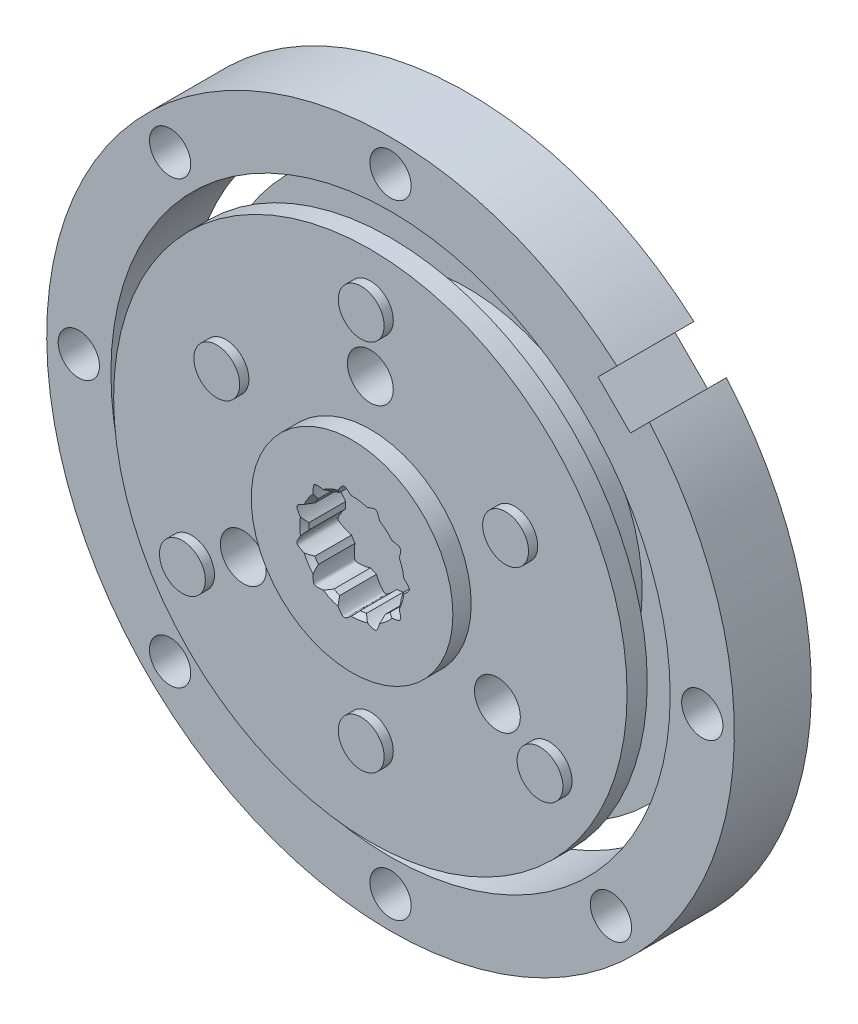
SolidWorks part; units mm, degrees
material "合金钢"
ref_plane "前视基准面" through (0, 0, 0) normal (0, 0, 1) x (1, 0, 0)
ref_plane "上视基准面" through (0, 0, 0) normal (0, 1, 0) x (1, 0, 0)
ref_plane "右视基准面" through (0, 0, 0) normal (1, 0, 0) x (0, 0, -1)
ref_axis "基准轴1" through (0, 0, 55) along (0, 0, -1)
sketch "旋转草图内花键" plane through (0, 0, 0) normal (1, 0, 0) x (0, 0, -1)
  line L0 (0, 0) -> (1, 0) construction
  line L1 (-12.7, 5.2) -> (-12.7, 19.05)
  line L2 (-12.7, 19.05) -> (12.7, 19.05)
  line L3 (12.7, 19.05) -> (12.7, 5.2)
  line L4 (12.7, 5.2) -> (-12.7, 5.2)
revolve "内花键" add sketch "旋转草图内花键" angle 360 about L0
sketch "齿草图内花键" plane through (0, 0, 0) normal (0, 0, 1) x (1, 0, 0)
  arc A0 (4.469, -1.3848) -> (4.469, 1.3848) centre (0, 0) ccw
  spline S0 degree 3 poles (4.469, 1.3848) (4.5766, 1.3527) (4.7413, 1.292) (4.9613, 1.1888) (5.1395, 1.0919) (5.3233, 0.9774) (5.5112, 0.8441) (5.7013, 0.6912) (5.8934, 0.5188) (6.0538, 0.3498) (6.1648, 0.2366) (6.2079, 0.1723) (6.2223, 0.1454) (6.2343, 0.1173) (6.2438, 0.0883) (6.257, 0.0305) (6.257, -0.0305) (6.2438, -0.0883) (6.2343, -0.1173) (6.2223, -0.1454) (6.2079, -0.1723) (6.1648, -0.2366) (6.0538, -0.3498) (5.8934, -0.5188) (5.7013, -0.6912) (5.5112, -0.8441) (5.3233, -0.9774) (5.1395, -1.0919) (4.9613, -1.1888) (4.7413, -1.292) (4.5766, -1.3527) (4.469, -1.3848) knots 0 0 0 0 0.072254 0.112805 0.156306 0.202756 0.252156 0.304505 0.359804 0.418052 0.454758 0.461299 0.467839 0.47438 0.48092 0.487461 0.512539 0.51908 0.52562 0.532161 0.538701 0.545242 0.581948 0.640196 0.695495 0.747844 0.797244 0.843694 0.887195 0.927746 1 1 1 1
extrude "齿拉伸切除内花键" cut sketch "齿草图内花键" against normal blind 12.7 and the other way blind 12.7
pattern_circular "齿形内花键" count 11 every 32.727 about axis through (0, 0, 55) along (0, 0, -1) of "齿拉伸切除内花键"
sketch "辅助草图内花键" plane through (0, 0, 0) normal (0, 0, 1) x (1, 0, 0)
  circle A0 centre (0, 0) radius 5.5 construction
  circle A1 centre (0, 0) radius 6.06 construction
  dimension "PitchDiameter" = 11
  dimension "FormDiameter" = 12.12
sketch "草图1" plane through (0, 0, 12.7) normal (0, 0, 1) x (1, 0, 0)
  circle A0 centre (0, 0) radius 11
  circle A1 centre (0, 0) radius 19.05 construction
  circle A2 centre (0, 0) radius 19.05
  dimension "D1" = 22
extrude "切除-拉伸1" cut sketch "草图1" against normal blind 2
sketch "草图2" plane through (0, 0, 10.7) normal (0, 0, 1) x (1, 0, 0)
  circle A0 centre (0, 0) radius 28
  circle A1 centre (0, 0) radius 19.05 construction
  circle A2 centre (0, 0) radius 19.05
  dimension "D1" = 56
extrude "凸台-拉伸1" add sketch "草图2" against normal blind 2.2
ref_plane "基准面1" through (0, 0, 8.5) normal (0, 0, 1) x (1, 0, 0)
sketch "草图4" plane through (0, 0, 8.5) normal (0, 0, 1) x (1, 0, 0)
  circle A0 centre (0, 0) radius 30.5
  circle A1 centre (0, 0) radius 37.5
  dimension "D1" = 61
  dimension "D2" = 75
extrude "凸台-拉伸3" add sketch "草图4" against normal blind 8.4 separate body
ref_plane "基准面2" through (0, 0, 4.3) normal (0, 0, 1) x (1, 0, 0)
mirror "镜向1" about plane through (0, 0, 4.3) normal (0, 0, 1) of "凸台-拉伸1"
sketch "草图5" plane through (0, 0, -12.7) normal (0, 0, -1) x (-1, 0, 0)
  circle A0 centre (0, 0) radius 19.05
extrude "切除-拉伸2" cut sketch "草图5" against normal up to surface (10.6 mm away) up to face at (28, 0, -2.1)
sketch "草图6" plane through (0, 0, -2.1) normal (0, 0, -1) x (-1, 0, 0)
  circle A1 centre (0, 0) radius 7.3279
extrude "凸台-拉伸4" add sketch "草图6" against normal blind 10.3
sketch "草图7" plane through (0, 0, -2.1) normal (0, 0, -1) x (-1, 0, 0)
  circle A0 centre (0, 0) radius 5
  dimension "D1" = 10
extrude "凸台-拉伸5" add sketch "草图7" along normal blind 2
sketch "草图8" plane through (0, 0, -4.1) normal (0, 0, -1) x (-1, 0, 0)
  arc A0 (4.2033, 4.2816) -> (3.6398, 4.7699) centre (0, 0) ccw
  arc A1 (1.2213, 5.8744) -> (0.4832, 5.9805) centre (0, 0) ccw
  arc A2 (-2.1485, 5.6021) -> (-2.8268, 5.2924) centre (0, 0) ccw
  arc A3 (-4.8362, 3.5512) -> (-5.2393, 2.9239) centre (0, 0) ccw
  arc A4 (-5.9884, 0.3728) -> (-5.9884, -0.3728) centre (0, 0) ccw
  arc A5 (-5.2393, -2.9239) -> (-4.8362, -3.5512) centre (0, 0) ccw
  arc A6 (-2.8268, -5.2924) -> (-2.1485, -5.6021) centre (0, 0) ccw
  arc A7 (0.4832, -5.9805) -> (1.2213, -5.8744) centre (0, 0) ccw
  arc A8 (3.6398, -4.7699) -> (4.2033, -4.2816) centre (0, 0) ccw
  arc A9 (5.6408, -2.0449) -> (5.8509, -1.3294) centre (0, 0) ccw
  arc A10 (5.8509, 1.3294) -> (5.6408, 2.0449) centre (0, 0) ccw
  spline S0 degree 3 poles (5.6408, 2.0449) (5.6059, 2.0647) (5.5481, 2.0966) (5.4671, 2.1391) (5.3987, 2.1734) (5.3308, 2.206) (5.2634, 2.2369) (5.1966, 2.2661) (5.1304, 2.2937) (5.0648, 2.3197) (4.9999, 2.3441) (4.9357, 2.367) (4.8723, 2.3883) (4.8096, 2.4082) (4.7477, 2.4266) (4.6867, 2.4436) (4.6265, 2.4593) (4.5673, 2.4736) (4.4879, 2.4914) (4.4166, 2.5045) (4.3542, 2.5189) (4.3219, 2.5307) (4.2909, 2.5455) (4.2615, 2.5634) (4.2341, 2.5842) (4.2089, 2.6077) (4.1862, 2.6335) (4.1704, 2.6559) (4.1595, 2.6732) (4.1484, 2.6902) (4.1345, 2.7139) (4.1205, 2.7453) (4.1096, 2.7779) (4.1021, 2.8115) (4.098, 2.8457) (4.0974, 2.88) (4.1001, 2.9144) (4.1129, 2.9771) (4.1306, 3.0474) (4.1474, 3.127) (4.159, 3.1868) (4.1697, 3.248) (4.1796, 3.3106) (4.1885, 3.3746) (4.1965, 3.4398) (4.2034, 3.5064) (4.2093, 3.5743) (4.214, 3.6435) (4.2177, 3.7139) (4.2201, 3.7856) (4.2212, 3.8585) (4.2211, 3.9326) (4.2197, 4.0079) (4.2169, 4.0844) (4.2119, 4.1758) (4.2069, 4.2416) (4.2033, 4.2816) knots 0.01157 0.01157 0.01157 0.01157 0.047599 0.070861 0.093765 0.116312 0.1385 0.16033 0.181802 0.202916 0.223673 0.244071 0.264111 0.283793 0.303117 0.322083 0.340691 0.358941 0.376833 0.413736 0.424017 0.434298 0.444579 0.45486 0.465141 0.475422 0.485703 0.495984 0.5 0.504016 0.514297 0.524578 0.534859 0.54514 0.555421 0.565702 0.575983 0.586264 0.623167 0.641059 0.659309 0.677917 0.696883 0.716207 0.735889 0.755929 0.776327 0.797084 0.818198 0.83967 0.8615 0.883688 0.906235 0.929139 0.952401 0.98843 0.98843 0.98843 0.98843
  spline S1 degree 3 poles (3.6398, 4.7699) (3.5997, 4.7677) (3.5339, 4.7634) (3.4427, 4.7552) (3.3666, 4.7471) (3.2919, 4.7378) (3.2185, 4.7274) (3.1465, 4.7159) (3.0759, 4.7033) (3.0067, 4.6897) (2.9389, 4.6751) (2.8725, 4.6597) (2.8076, 4.6433) (2.7441, 4.6262) (2.6821, 4.6082) (2.6216, 4.5895) (2.5625, 4.5702) (2.5049, 4.5502) (2.4285, 4.5223) (2.3615, 4.4947) (2.3012, 4.4731) (2.2676, 4.4656) (2.2335, 4.4612) (2.1991, 4.4604) (2.1648, 4.4631) (2.1309, 4.4692) (2.0979, 4.4787) (2.0725, 4.489) (2.054, 4.4976) (2.0354, 4.5059) (2.0109, 4.5184) (1.9821, 4.5372) (1.9553, 4.5587) (1.9309, 4.5829) (1.909, 4.6094) (1.8899, 4.6381) (1.8736, 4.6684) (1.8504, 4.7281) (1.8274, 4.7968) (1.7984, 4.8728) (1.7758, 4.9294) (1.7518, 4.9868) (1.7263, 5.0447) (1.6992, 5.1034) (1.6706, 5.1626) (1.6404, 5.2223) (1.6087, 5.2826) (1.5753, 5.3434) (1.5402, 5.4046) (1.5035, 5.4662) (1.4651, 5.5282) (1.4249, 5.5905) (1.383, 5.653) (1.3393, 5.7158) (1.2857, 5.7901) (1.2459, 5.8427) (1.2213, 5.8744) knots 0.01157 0.01157 0.01157 0.01157 0.047599 0.070861 0.093765 0.116312 0.1385 0.16033 0.181802 0.202916 0.223673 0.244071 0.264111 0.283793 0.303117 0.322083 0.340691 0.358941 0.376833 0.413736 0.424017 0.434298 0.444579 0.45486 0.465141 0.475422 0.485703 0.495984 0.5 0.504016 0.514297 0.524578 0.534859 0.54514 0.555421 0.565702 0.575983 0.586264 0.623167 0.641059 0.659309 0.677917 0.696883 0.716207 0.735889 0.755929 0.776327 0.797084 0.818198 0.83967 0.8615 0.883688 0.906235 0.929139 0.952401 0.98843 0.98843 0.98843 0.98843
  spline S2 degree 3 poles (0.4832, 5.9805) (0.4507, 5.9571) (0.3976, 5.9177) (0.3253, 5.8616) (0.2657, 5.8137) (0.2078, 5.7654) (0.1518, 5.717) (0.0974, 5.6684) (0.0448, 5.6196) (-0.0061, 5.5707) (-0.0552, 5.5218) (-0.1027, 5.4729) (-0.1485, 5.4241) (-0.1926, 5.3753) (-0.2351, 5.3267) (-0.2759, 5.2783) (-0.3151, 5.2301) (-0.3527, 5.1821) (-0.402, 5.1173) (-0.4434, 5.0579) (-0.4825, 5.0071) (-0.5066, 4.9826) (-0.533, 4.9605) (-0.5615, 4.9413) (-0.5918, 4.925) (-0.6236, 4.9118) (-0.6565, 4.9019) (-0.6835, 4.8968) (-0.7037, 4.8941) (-0.7238, 4.891) (-0.7511, 4.8883) (-0.7855, 4.8885) (-0.8197, 4.8922) (-0.8534, 4.8993) (-0.8861, 4.9098) (-0.9177, 4.9235) (-0.9478, 4.9402) (-0.9995, 4.9779) (-1.056, 5.0233) (-1.1215, 5.0716) (-1.1711, 5.107) (-1.2223, 5.1422) (-1.2752, 5.1772) (-1.3296, 5.2119) (-1.3857, 5.2462) (-1.4434, 5.2802) (-1.5027, 5.3137) (-1.5636, 5.3468) (-1.6262, 5.3793) (-1.6904, 5.4113) (-1.7563, 5.4427) (-1.8237, 5.4733) (-1.8928, 5.5033) (-1.9635, 5.5325) (-2.0487, 5.566) (-2.1107, 5.5888) (-2.1485, 5.6021) knots 0.01157 0.01157 0.01157 0.01157 0.047599 0.070861 0.093765 0.116312 0.1385 0.16033 0.181802 0.202916 0.223673 0.244071 0.264111 0.283793 0.303117 0.322083 0.340691 0.358941 0.376833 0.413736 0.424017 0.434298 0.444579 0.45486 0.465141 0.475422 0.485703 0.495984 0.5 0.504016 0.514297 0.524578 0.534859 0.54514 0.555421 0.565702 0.575983 0.586264 0.623167 0.641059 0.659309 0.677917 0.696883 0.716207 0.735889 0.755929 0.776327 0.797084 0.818198 0.83967 0.8615 0.883688 0.906235 0.929139 0.952401 0.98843 0.98843 0.98843 0.98843
  spline S3 degree 3 poles (-2.8268, 5.2924) (-2.8415, 5.255) (-2.8649, 5.1933) (-2.8954, 5.107) (-2.9196, 5.0344) (-2.9422, 4.9626) (-2.9632, 4.8915) (-2.9826, 4.8212) (-3.0005, 4.7517) (-3.0169, 4.6831) (-3.0318, 4.6154) (-3.0453, 4.5486) (-3.0574, 4.4828) (-3.0682, 4.4179) (-3.0776, 4.3541) (-3.0858, 4.2912) (-3.0927, 4.2294) (-3.0984, 4.1688) (-3.1048, 4.0877) (-3.1075, 4.0153) (-3.1129, 3.9514) (-3.12, 3.9177) (-3.1303, 3.8849) (-3.1438, 3.8533) (-3.1605, 3.8232) (-3.1801, 3.795) (-3.2024, 3.7688) (-3.2224, 3.75) (-3.2379, 3.7368) (-3.2532, 3.7233) (-3.2747, 3.7062) (-3.3037, 3.6878) (-3.3345, 3.6724) (-3.3667, 3.6602) (-3.3999, 3.6513) (-3.4338, 3.6458) (-3.4682, 3.6436) (-3.5321, 3.6473) (-3.6042, 3.6549) (-3.6854, 3.6601) (-3.7463, 3.6631) (-3.8084, 3.6651) (-3.8717, 3.6659) (-3.9363, 3.6657) (-4.002, 3.6642) (-4.0689, 3.6616) (-4.137, 3.6578) (-4.2061, 3.6526) (-4.2763, 3.6462) (-4.3476, 3.6384) (-4.42, 3.6291) (-4.4933, 3.6185) (-4.5677, 3.6064) (-4.643, 3.5927) (-4.7327, 3.5748) (-4.7972, 3.5605) (-4.8362, 3.5512) knots 0.01157 0.01157 0.01157 0.01157 0.047599 0.070861 0.093765 0.116312 0.1385 0.16033 0.181802 0.202916 0.223673 0.244071 0.264111 0.283793 0.303117 0.322083 0.340691 0.358941 0.376833 0.413736 0.424017 0.434298 0.444579 0.45486 0.465141 0.475422 0.485703 0.495984 0.5 0.504016 0.514297 0.524578 0.534859 0.54514 0.555421 0.565702 0.575983 0.586264 0.623167 0.641059 0.659309 0.677917 0.696883 0.716207 0.735889 0.755929 0.776327 0.797084 0.818198 0.83967 0.8615 0.883688 0.906235 0.929139 0.952401 0.98843 0.98843 0.98843 0.98843
  spline S4 degree 3 poles (-5.2393, 2.9239) (-5.2315, 2.8846) (-5.2178, 2.82) (-5.1968, 2.7309) (-5.1779, 2.6568) (-5.1581, 2.5841) (-5.1373, 2.513) (-5.1156, 2.4433) (-5.0931, 2.3752) (-5.0698, 2.3086) (-5.0458, 2.2436) (-5.021, 2.1801) (-4.9956, 2.1182) (-4.9696, 2.0578) (-4.943, 1.999) (-4.9159, 1.9417) (-4.8884, 1.886) (-4.8603, 1.8319) (-4.8219, 1.7602) (-4.785, 1.6978) (-4.7551, 1.6412) (-4.7428, 1.609) (-4.7337, 1.5759) (-4.728, 1.5419) (-4.7257, 1.5076) (-4.727, 1.4732) (-4.7316, 1.4391) (-4.7382, 1.4125) (-4.7442, 1.393) (-4.7497, 1.3734) (-4.7585, 1.3474) (-4.7731, 1.3163) (-4.7906, 1.2867) (-4.8111, 1.259) (-4.8342, 1.2335) (-4.8598, 1.2106) (-4.8875, 1.1901) (-4.9433, 1.1587) (-5.008, 1.1261) (-5.0792, 1.0866) (-5.132, 1.0562) (-5.1853, 1.0243) (-5.2391, 0.9907) (-5.2932, 0.9556) (-5.3478, 0.9189) (-5.4026, 0.8805) (-5.4578, 0.8405) (-5.5132, 0.7988) (-5.5688, 0.7554) (-5.6245, 0.7103) (-5.6804, 0.6634) (-5.7363, 0.6148) (-5.7923, 0.5644) (-5.8483, 0.5122) (-5.9141, 0.4486) (-5.9606, 0.4017) (-5.9884, 0.3728) knots 0.01157 0.01157 0.01157 0.01157 0.047599 0.070861 0.093765 0.116312 0.1385 0.16033 0.181802 0.202916 0.223673 0.244071 0.264111 0.283793 0.303117 0.322083 0.340691 0.358941 0.376833 0.413736 0.424017 0.434298 0.444579 0.45486 0.465141 0.475422 0.485703 0.495984 0.5 0.504016 0.514297 0.524578 0.534859 0.54514 0.555421 0.565702 0.575983 0.586264 0.623167 0.641059 0.659309 0.677917 0.696883 0.716207 0.735889 0.755929 0.776327 0.797084 0.818198 0.83967 0.8615 0.883688 0.906235 0.929139 0.952401 0.98843 0.98843 0.98843 0.98843
  spline S5 degree 3 poles (-5.9884, -0.3728) (-5.9606, -0.4017) (-5.9141, -0.4486) (-5.8483, -0.5122) (-5.7923, -0.5644) (-5.7363, -0.6148) (-5.6804, -0.6634) (-5.6245, -0.7103) (-5.5688, -0.7554) (-5.5132, -0.7988) (-5.4578, -0.8405) (-5.4026, -0.8805) (-5.3478, -0.9189) (-5.2932, -0.9556) (-5.2391, -0.9907) (-5.1853, -1.0243) (-5.132, -1.0562) (-5.0792, -1.0866) (-5.008, -1.1261) (-4.9433, -1.1587) (-4.8875, -1.1901) (-4.8598, -1.2106) (-4.8342, -1.2335) (-4.8111, -1.259) (-4.7906, -1.2867) (-4.7731, -1.3163) (-4.7585, -1.3474) (-4.7497, -1.3734) (-4.7442, -1.393) (-4.7382, -1.4125) (-4.7316, -1.4391) (-4.727, -1.4732) (-4.7257, -1.5076) (-4.728, -1.5419) (-4.7337, -1.5759) (-4.7428, -1.609) (-4.7551, -1.6412) (-4.785, -1.6978) (-4.8219, -1.7602) (-4.8603, -1.8319) (-4.8884, -1.886) (-4.9159, -1.9417) (-4.943, -1.999) (-4.9696, -2.0578) (-4.9956, -2.1182) (-5.021, -2.1801) (-5.0458, -2.2436) (-5.0698, -2.3086) (-5.0931, -2.3752) (-5.1156, -2.4433) (-5.1373, -2.513) (-5.1581, -2.5841) (-5.1779, -2.6568) (-5.1968, -2.7309) (-5.2178, -2.82) (-5.2315, -2.8846) (-5.2393, -2.9239) knots 0.01157 0.01157 0.01157 0.01157 0.047599 0.070861 0.093765 0.116312 0.1385 0.16033 0.181802 0.202916 0.223673 0.244071 0.264111 0.283793 0.303117 0.322083 0.340691 0.358941 0.376833 0.413736 0.424017 0.434298 0.444579 0.45486 0.465141 0.475422 0.485703 0.495984 0.5 0.504016 0.514297 0.524578 0.534859 0.54514 0.555421 0.565702 0.575983 0.586264 0.623167 0.641059 0.659309 0.677917 0.696883 0.716207 0.735889 0.755929 0.776327 0.797084 0.818198 0.83967 0.8615 0.883688 0.906235 0.929139 0.952401 0.98843 0.98843 0.98843 0.98843
  spline S6 degree 3 poles (-4.8362, -3.5512) (-4.7972, -3.5605) (-4.7327, -3.5748) (-4.643, -3.5927) (-4.5677, -3.6064) (-4.4933, -3.6185) (-4.42, -3.6291) (-4.3476, -3.6384) (-4.2763, -3.6462) (-4.2061, -3.6526) (-4.137, -3.6578) (-4.0689, -3.6616) (-4.002, -3.6642) (-3.9363, -3.6657) (-3.8717, -3.6659) (-3.8084, -3.6651) (-3.7463, -3.6631) (-3.6854, -3.6601) (-3.6042, -3.6549) (-3.5321, -3.6473) (-3.4682, -3.6436) (-3.4338, -3.6458) (-3.3999, -3.6513) (-3.3667, -3.6602) (-3.3345, -3.6724) (-3.3037, -3.6878) (-3.2747, -3.7062) (-3.2532, -3.7233) (-3.2379, -3.7368) (-3.2224, -3.75) (-3.2024, -3.7688) (-3.1801, -3.795) (-3.1605, -3.8232) (-3.1438, -3.8533) (-3.1303, -3.8849) (-3.12, -3.9177) (-3.1129, -3.9514) (-3.1075, -4.0153) (-3.1048, -4.0877) (-3.0984, -4.1688) (-3.0927, -4.2294) (-3.0858, -4.2912) (-3.0776, -4.3541) (-3.0682, -4.4179) (-3.0574, -4.4828) (-3.0453, -4.5486) (-3.0318, -4.6154) (-3.0169, -4.6831) (-3.0005, -4.7517) (-2.9826, -4.8212) (-2.9632, -4.8915) (-2.9422, -4.9626) (-2.9196, -5.0344) (-2.8954, -5.107) (-2.8649, -5.1933) (-2.8415, -5.255) (-2.8268, -5.2924) knots 0.01157 0.01157 0.01157 0.01157 0.047599 0.070861 0.093765 0.116312 0.1385 0.16033 0.181802 0.202916 0.223673 0.244071 0.264111 0.283793 0.303117 0.322083 0.340691 0.358941 0.376833 0.413736 0.424017 0.434298 0.444579 0.45486 0.465141 0.475422 0.485703 0.495984 0.5 0.504016 0.514297 0.524578 0.534859 0.54514 0.555421 0.565702 0.575983 0.586264 0.623167 0.641059 0.659309 0.677917 0.696883 0.716207 0.735889 0.755929 0.776327 0.797084 0.818198 0.83967 0.8615 0.883688 0.906235 0.929139 0.952401 0.98843 0.98843 0.98843 0.98843
  spline S7 degree 3 poles (-2.1485, -5.6021) (-2.1107, -5.5888) (-2.0487, -5.566) (-1.9635, -5.5325) (-1.8928, -5.5033) (-1.8237, -5.4733) (-1.7563, -5.4427) (-1.6904, -5.4113) (-1.6262, -5.3793) (-1.5636, -5.3468) (-1.5027, -5.3137) (-1.4434, -5.2802) (-1.3857, -5.2462) (-1.3296, -5.2119) (-1.2752, -5.1772) (-1.2223, -5.1422) (-1.1711, -5.107) (-1.1215, -5.0716) (-1.056, -5.0233) (-0.9995, -4.9779) (-0.9478, -4.9402) (-0.9177, -4.9235) (-0.8861, -4.9098) (-0.8534, -4.8993) (-0.8197, -4.8922) (-0.7855, -4.8885) (-0.7511, -4.8883) (-0.7238, -4.891) (-0.7037, -4.8941) (-0.6835, -4.8968) (-0.6565, -4.9019) (-0.6236, -4.9118) (-0.5918, -4.925) (-0.5615, -4.9413) (-0.533, -4.9605) (-0.5066, -4.9826) (-0.4825, -5.0071) (-0.4434, -5.0579) (-0.402, -5.1173) (-0.3527, -5.1821) (-0.3151, -5.2301) (-0.2759, -5.2783) (-0.2351, -5.3267) (-0.1926, -5.3753) (-0.1485, -5.4241) (-0.1027, -5.4729) (-0.0552, -5.5218) (-0.0061, -5.5707) (0.0448, -5.6196) (0.0974, -5.6684) (0.1518, -5.717) (0.2078, -5.7654) (0.2657, -5.8137) (0.3253, -5.8616) (0.3976, -5.9177) (0.4507, -5.9571) (0.4832, -5.9805) knots 0.01157 0.01157 0.01157 0.01157 0.047599 0.070861 0.093765 0.116312 0.1385 0.16033 0.181802 0.202916 0.223673 0.244071 0.264111 0.283793 0.303117 0.322083 0.340691 0.358941 0.376833 0.413736 0.424017 0.434298 0.444579 0.45486 0.465141 0.475422 0.485703 0.495984 0.5 0.504016 0.514297 0.524578 0.534859 0.54514 0.555421 0.565702 0.575983 0.586264 0.623167 0.641059 0.659309 0.677917 0.696883 0.716207 0.735889 0.755929 0.776327 0.797084 0.818198 0.83967 0.8615 0.883688 0.906235 0.929139 0.952401 0.98843 0.98843 0.98843 0.98843
  spline S8 degree 3 poles (1.2213, -5.8744) (1.2459, -5.8427) (1.2857, -5.7901) (1.3393, -5.7158) (1.383, -5.653) (1.4249, -5.5905) (1.4651, -5.5282) (1.5035, -5.4662) (1.5402, -5.4046) (1.5753, -5.3434) (1.6087, -5.2826) (1.6404, -5.2223) (1.6706, -5.1626) (1.6992, -5.1034) (1.7263, -5.0447) (1.7518, -4.9868) (1.7758, -4.9294) (1.7984, -4.8728) (1.8274, -4.7968) (1.8504, -4.7281) (1.8736, -4.6684) (1.8899, -4.6381) (1.909, -4.6094) (1.9309, -4.5829) (1.9553, -4.5587) (1.9821, -4.5372) (2.0109, -4.5184) (2.0354, -4.5059) (2.054, -4.4976) (2.0725, -4.489) (2.0979, -4.4787) (2.1309, -4.4692) (2.1648, -4.4631) (2.1991, -4.4604) (2.2335, -4.4612) (2.2676, -4.4656) (2.3012, -4.4731) (2.3615, -4.4947) (2.4285, -4.5223) (2.5049, -4.5502) (2.5625, -4.5702) (2.6216, -4.5895) (2.6821, -4.6082) (2.7441, -4.6262) (2.8076, -4.6433) (2.8725, -4.6597) (2.9389, -4.6751) (3.0067, -4.6897) (3.0759, -4.7033) (3.1465, -4.7159) (3.2185, -4.7274) (3.2919, -4.7378) (3.3666, -4.7471) (3.4427, -4.7552) (3.5339, -4.7634) (3.5997, -4.7677) (3.6398, -4.7699) knots 0.01157 0.01157 0.01157 0.01157 0.047599 0.070861 0.093765 0.116312 0.1385 0.16033 0.181802 0.202916 0.223673 0.244071 0.264111 0.283793 0.303117 0.322083 0.340691 0.358941 0.376833 0.413736 0.424017 0.434298 0.444579 0.45486 0.465141 0.475422 0.485703 0.495984 0.5 0.504016 0.514297 0.524578 0.534859 0.54514 0.555421 0.565702 0.575983 0.586264 0.623167 0.641059 0.659309 0.677917 0.696883 0.716207 0.735889 0.755929 0.776327 0.797084 0.818198 0.83967 0.8615 0.883688 0.906235 0.929139 0.952401 0.98843 0.98843 0.98843 0.98843
  spline S9 degree 3 poles (4.2033, -4.2816) (4.2069, -4.2416) (4.2119, -4.1758) (4.2169, -4.0844) (4.2197, -4.0079) (4.2211, -3.9326) (4.2212, -3.8585) (4.2201, -3.7856) (4.2177, -3.7139) (4.214, -3.6435) (4.2093, -3.5743) (4.2034, -3.5064) (4.1965, -3.4398) (4.1885, -3.3746) (4.1796, -3.3106) (4.1697, -3.248) (4.159, -3.1868) (4.1474, -3.127) (4.1306, -3.0474) (4.1129, -2.9771) (4.1001, -2.9144) (4.0974, -2.88) (4.098, -2.8457) (4.1021, -2.8115) (4.1096, -2.7779) (4.1205, -2.7453) (4.1345, -2.7139) (4.1484, -2.6902) (4.1595, -2.6732) (4.1704, -2.6559) (4.1862, -2.6335) (4.2089, -2.6077) (4.2341, -2.5842) (4.2615, -2.5634) (4.2909, -2.5455) (4.3219, -2.5307) (4.3542, -2.5189) (4.4166, -2.5045) (4.4879, -2.4914) (4.5673, -2.4736) (4.6265, -2.4593) (4.6867, -2.4436) (4.7477, -2.4266) (4.8096, -2.4082) (4.8723, -2.3883) (4.9357, -2.367) (4.9999, -2.3441) (5.0648, -2.3197) (5.1304, -2.2937) (5.1966, -2.2661) (5.2634, -2.2369) (5.3308, -2.206) (5.3987, -2.1734) (5.4671, -2.1391) (5.5481, -2.0966) (5.6059, -2.0647) (5.6408, -2.0449) knots 0.01157 0.01157 0.01157 0.01157 0.047599 0.070861 0.093765 0.116312 0.1385 0.16033 0.181802 0.202916 0.223673 0.244071 0.264111 0.283793 0.303117 0.322083 0.340691 0.358941 0.376833 0.413736 0.424017 0.434298 0.444579 0.45486 0.465141 0.475422 0.485703 0.495984 0.5 0.504016 0.514297 0.524578 0.534859 0.54514 0.555421 0.565702 0.575983 0.586264 0.623167 0.641059 0.659309 0.677917 0.696883 0.716207 0.735889 0.755929 0.776327 0.797084 0.818198 0.83967 0.8615 0.883688 0.906235 0.929139 0.952401 0.98843 0.98843 0.98843 0.98843
  spline S10 degree 3 poles (5.8509, -1.3294) (5.8323, -1.2939) (5.8009, -1.2358) (5.7557, -1.1562) (5.7167, -1.0904) (5.6772, -1.0262) (5.6372, -0.9638) (5.5968, -0.9031) (5.556, -0.8441) (5.5149, -0.7868) (5.4735, -0.7312) (5.4319, -0.6772) (5.39, -0.625) (5.348, -0.5744) (5.306, -0.5254) (5.2638, -0.4781) (5.2217, -0.4324) (5.1796, -0.3883) (5.1224, -0.3304) (5.0695, -0.2809) (5.0248, -0.235) (5.004, -0.2076) (4.9859, -0.1784) (4.9709, -0.1474) (4.9591, -0.1151) (4.9506, -0.0818) (4.9454, -0.0478) (4.9443, -0.0204) (4.9444, 0) (4.9443, 0.0204) (4.9454, 0.0478) (4.9506, 0.0818) (4.9591, 0.1151) (4.9709, 0.1474) (4.9859, 0.1784) (5.004, 0.2076) (5.0248, 0.235) (5.0695, 0.2809) (5.1224, 0.3304) (5.1796, 0.3883) (5.2217, 0.4324) (5.2638, 0.4781) (5.306, 0.5254) (5.348, 0.5744) (5.39, 0.625) (5.4319, 0.6772) (5.4735, 0.7312) (5.5149, 0.7868) (5.556, 0.8441) (5.5968, 0.9031) (5.6372, 0.9638) (5.6772, 1.0262) (5.7167, 1.0904) (5.7557, 1.1562) (5.8009, 1.2358) (5.8323, 1.2939) (5.8509, 1.3294) knots 0.01157 0.01157 0.01157 0.01157 0.047599 0.070861 0.093765 0.116312 0.1385 0.16033 0.181802 0.202916 0.223673 0.244071 0.264111 0.283793 0.303117 0.322083 0.340691 0.358941 0.376833 0.413736 0.424017 0.434298 0.444579 0.45486 0.465141 0.475422 0.485703 0.495984 0.5 0.504016 0.514297 0.524578 0.534859 0.54514 0.555421 0.565702 0.575983 0.586264 0.623167 0.641059 0.659309 0.677917 0.696883 0.716207 0.735889 0.755929 0.776327 0.797084 0.818198 0.83967 0.8615 0.883688 0.906235 0.929139 0.952401 0.98843 0.98843 0.98843 0.98843
extrude "凸台-拉伸6" add sketch "草图8" along normal blind 5.8
sketch "草图9" plane through (0, 0, 8.5) normal (0, 0, 1) x (1, 0, 0)
  line L0 (0, 0) -> (33.1112, 33.1112) construction
  line L1 (26.163, 22.6274) -> (28.2253, 24.6897)
  line L2 (22.6274, 26.163) -> (24.6897, 28.2253)
  line L3 (22.6274, 26.163) -> (26.163, 22.6274)
  line L5 (-1.7678, 1.7678) -> (31.3435, 34.879) construction
  line L6 (1.7678, -1.7678) -> (34.879, 31.3435) construction
  circle A0 centre (0, 0) radius 34 construction
  circle A1 centre (0, 34) radius 2.25
  circle A2 centre (24.0416, 24.0416) radius 2.25 construction
  circle A3 centre (34, 0) radius 2.25
  circle A4 centre (24.0416, -24.0416) radius 2.25
  circle A5 centre (0, -34) radius 2.25
  circle A6 centre (-24.0416, -24.0416) radius 2.25
  circle A7 centre (-34, 0) radius 2.25
  circle A8 centre (-24.0416, 24.0416) radius 2.25
  circle A9 centre (0, 0) radius 37.5 construction
  arc A10 (28.2253, 24.6897) -> (24.6897, 28.2253) centre (0, 0) ccw
  point P21 (0, 0)
  dimension "D1" = 68
  dimension "D2" = 4.5
  dimension "D6" = 34.5
  dimension "D4" = 2.5
  dimension "D5" = 2.5
  dimension "D3" = 8
extrude "切除-拉伸3" cut sketch "草图9" against normal up to surface (8.4 mm away) up to face at (30.5, 0, 0.1)
sketch "草图10" plane through (0, 0, 10.7) normal (0, 0, 1) x (1, 0, 0)
  line L0 (0, 0) -> (0, 34) construction
  line L1 (0, 0) -> (15.75, 9.0933) construction
  line L2 (0, 22.5167) -> (-19.5, -11.2583) construction
  line L3 (-19.5, -11.2583) -> (19.5, -11.2583) construction
  line L4 (19.5, -11.2583) -> (0, 22.5167) construction
  line L6 (15.75, 9.0933) -> (-15.75, 9.0933) construction
  line L7 (-15.75, 9.0933) -> (0, -18.1865) construction
  line L8 (0, -18.1865) -> (15.75, 9.0933) construction
  circle A8 centre (0, 0) radius 11.2583 construction
  circle A9 centre (0, 0) radius 9.0933 construction
  circle A10 centre (0, 22.5167) radius 2.5
  circle A11 centre (19.5, -11.2583) radius 2.5
  circle A12 centre (-19.5, -11.2583) radius 2.5
  circle A13 centre (15.75, 9.0933) radius 2.5
  circle A14 centre (0, -18.1865) radius 2.5
  circle A15 centre (-15.75, 9.0933) radius 2.5
  point P17 (0, 0)
  point P25 (0, 0)
  point P30 (0, 0)
  dimension "D1" = 5
  dimension "D2" = 3
  dimension "D3" = 5
  dimension "D4" = 3
extrude "凸台-拉伸7" add sketch "草图10" along normal blind 1
sketch "草图11" plane through (0, 0, -2.1) normal (0, 0, -1) x (-1, 0, 0)
  line L0 (0, 0) -> (0, 34) construction
  line L1 (-19.5, -11.2583) -> (0, 22.5167) construction
  line L2 (0, 22.5167) -> (-19.5, -11.2583) construction
  line L3 (-19.5, -11.2583) -> (19.5, -11.2583) construction
  line L4 (19.5, -11.2583) -> (0, 22.5167) construction
  line L5 (0, 0) -> (-15.75, 9.0933) construction
  line L7 (-15.75, 9.0933) -> (0, -18.1865) construction
  line L8 (0, -18.1865) -> (15.75, 9.0933) construction
  line L9 (15.75, 9.0933) -> (-15.75, 9.0933) construction
  circle A1 centre (0, 0) radius 11.2583 construction
  circle A11 centre (0, 22.5167) radius 2.5
  circle A12 centre (-19.5, -11.2583) radius 2.5
  circle A13 centre (19.5, -11.2583) radius 2.5
  circle A14 centre (0, 0) radius 9.0933 construction
  circle A15 centre (-15.75, 9.0933) radius 2.5
  circle A16 centre (15.75, 9.0933) radius 2.5
  circle A17 centre (0, -18.1865) radius 2.5
  point P18 (0, 0)
  point P33 (0, 0)
  dimension "D1" = 5
  dimension "D2" = 5
  dimension "D3" = 5
  dimension "D4" = 5
  dimension "D5" = 3
extrude "凸台-拉伸8" add sketch "草图11" along normal blind 1
chamfer "倒角1" distance 0.5 angle 45 22 edges at (2.4925, -5.4578, -9.9) (5.0475, -3.2438, -9.9) (6, 0, -9.9) (5.0475, 3.2438, -9.9) (2.4925, 5.4578, -9.9) (-0.8539, 5.9389, -9.9) (-3.9292, 4.5345, -9.9) (-5.757, 1.6904, -9.9) (-5.757, -1.6904, -9.9) (-0.8539, -5.9389, -9.9) (-3.9292, -4.5345, -9.9) (-2.1602, 4.7301, 12.7) (0.74, 5.1471, 12.7) (3.4053, 3.9299, 12.7) (4.9894, 1.465, 12.7) (4.9894, -1.465, 12.7) (3.4053, -3.9299, 12.7) (0.74, -5.1471, 12.7) (-2.1602, -4.7301, 12.7) (-4.3745, -2.8113, 12.7) (-5.2, 0, 12.7) (-4.3745, 2.8113, 12.7)
sketch "草图13" plane through (0, 0, -2.1) normal (0, 0, -1) x (-1, 0, 0)
  circle A0 centre (0, 0) radius 16 construction
  circle A1 centre (0, 16) radius 2.5
  circle A2 centre (13.8564, -8) radius 2.5
  circle A3 centre (-13.8564, -8) radius 2.5
  point P11 (0, 0)
  dimension "D1" = 32
  dimension "D2" = 5
  dimension "D3" = 3
extrude "切除-拉伸5" cut sketch "草图13" against normal blind 22
sketch "草图15" plane through (0, 0, -2.1) normal (0, 0, -1) x (-1, 0, 0)
  circle A0 centre (0, 0) radius 11 construction
  dimension "D1" = 22
equation "\"1。5\"=1"
